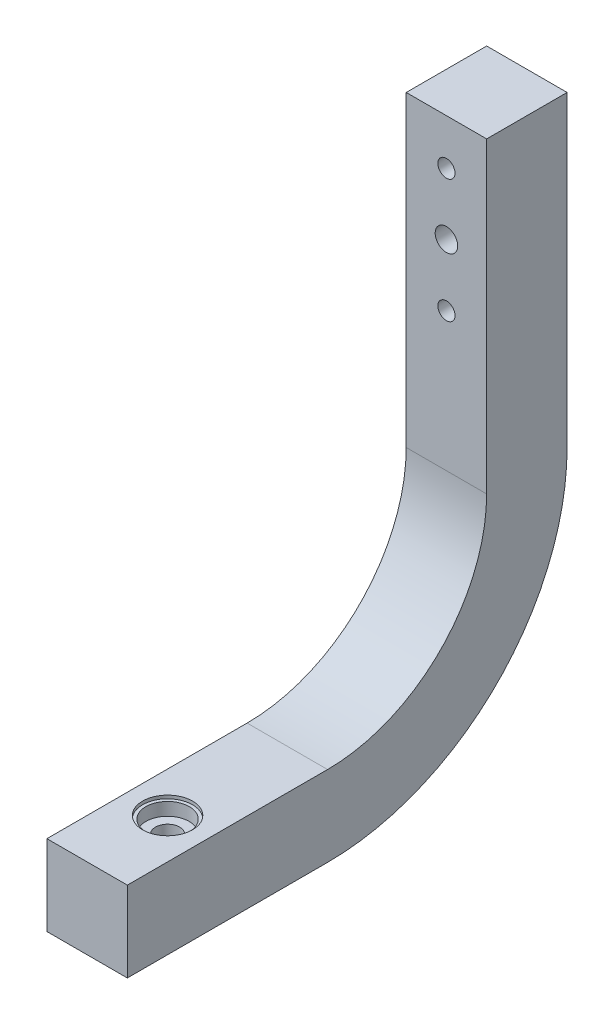
SolidWorks part; units mm, degrees
ref_plane "Front Plane" through (0, 0, 0) normal (0, 0, 1) x (1, 0, 0)
ref_plane "Top Plane" through (0, 0, 0) normal (0, 1, 0) x (1, 0, 0)
ref_plane "Right Plane" through (0, 0, 0) normal (1, 0, 0) x (0, 0, -1)
ref_axis "Z" through (0, 0, 86.1) along (0, 0, -1)
sketch "Sketch1" plane through (0, 0, 0) normal (1, 0, 0) x (0, 0, -1)
  line L0 (-15, 20) -> (0, 20)
  line L1 (0, 20) -> (0, -37.3333)
  line L2 (0, -32) -> (-50, -82) construction
  line L3 (-44.6667, -82) -> (-67, -82)
  line L4 (-67, -82) -> (-67, -67) construction
  line L5 (-67, -67) -> (-44.6667, -67)
  line L6 (-56.2132, -67) -> (-15, -25.7868) construction
  line L7 (-15, -37.3333) -> (-15, 20)
  line L8 (-35.6066, -46.3934) -> (-25, -57) construction
  line L9 (-44.6667, -67) -> (-56.2132, -67) construction
  line L10 (-67, -67) -> (-82, -67)
  line L11 (-67, -67) -> (-67, -82) construction
  line L12 (-67, -82) -> (-82, -82)
  line L13 (-82, -67) -> (-82, -82)
  line L14 (-15, -25.7868) -> (-15, -37.3333) construction
  line L15 (0, -37.3333) -> (0, -32) construction
  line L16 (-50, -82) -> (-44.6667, -82) construction
  arc A0 (-44.6667, -67) -> (-15, -37.3333) centre (-44.6667, -37.3333) ccw
  arc A1 (-44.6667, -82) -> (0, -37.3333) centre (-44.6667, -37.3333) ccw
  dimension "D1" = 15
  dimension "D2" = 67
  dimension "D3" = 82
  dimension "D4" = 20
  dimension "D5" = 135
  dimension "D6" = 50
  dimension "D7" = 15
  dimension "D8" = 22.3333
extrude "Boss-Extrude1" add sketch "Sketch1" along normal blind 7.5 and the other way blind 7.5
sketch "Sketch3" plane through (0, -67, 0) normal (0, 1, 0) x (1, 0, 0)
  line L0 (-8.25, 0) -> (8.25, 0) construction
  line L1 (0, -45.1) -> (0, 45.1) construction
  circle A0 centre (0, -67) radius 2.25
  dimension "D2" = 4.5
  dimension "D1" = 67
extrude "Cut-Extrude1" cut sketch "Sketch3" against normal through all
sketch "Sketch4" plane through (0, 0, 15) normal (0, 0, 1) x (1, 0, 0)
  line L0 (0, -11.5) -> (0, 11.5) construction
  circle A0 centre (0, 0) radius 2.1
  circle A1 centre (0, 11.5) radius 1.6
  circle A2 centre (0, -11.5) radius 1.6
  dimension "D1" = 4.2
  dimension "D3" = 3.2
  dimension "D2" = 23
extrude "Cut-Extrude2" cut sketch "Sketch4" against normal through all both and the other way through all
ref_axis "Axis1" through (0, -52.3642, 67) along (0, 1, 0)
sketch "Sketch5" plane through (0, 0, 0) normal (1, 0, 0) x (0, 0, -1)
  line L0 (-62.95, -79) -> (-62.95, -81.4)
  line L1 (-62.95, -81.4) -> (-62.35, -81.4)
  line L2 (-62.35, -81.4) -> (-62.35, -82)
  line L3 (-62.35, -82) -> (-67, -82)
  line L4 (-67, -82) -> (-67, -79)
  line L5 (-67, -79) -> (-62.95, -79)
  line L6 (-67, -74.5) -> (-67, -90.6731) construction
  line L7 (-67, -74.5) -> (-82, -74.5) construction
  line L8 (-67, -70) -> (-62.95, -70)
  line L9 (-67, -67) -> (-67, -70)
  line L10 (-62.35, -67) -> (-67, -67)
  line L11 (-62.35, -67.6) -> (-62.35, -67)
  line L12 (-62.95, -67.6) -> (-62.35, -67.6)
  line L13 (-62.95, -70) -> (-62.95, -67.6)
  line L16 (-67, -52.3642) -> (-67, -36.7401) construction
  line L17 (-82, -67) -> (-82, -82) construction
  line L18 (-67, -67) -> (-44.6667, -67) construction
  dimension "D2" = 4.65
  dimension "D3" = 3
  dimension "D4" = 8.1
revolve "Cut-Revolve1" cut sketch "Sketch5" angle 360 about axis through (0, -52.3642, 67) along (0, 1, 0)
equation "\"rbracket-width\"= \"L2Thickness\""
equation "\"D1@Boss-Extrude1\"=\"rbracket-width\"/2"
equation "\"D2@Boss-Extrude1\"=\"rbracket-width\"/2"
equation "\"EyeCaptureRadius\"= ( \"EyeDiameter\" + \"EyeClearance\" ) / 2"
equation "\"rbracket_planetocenterline_dist\"= \"BasePlaneDistance\""
equation "\"D2@Sketch1\"=\"rbracket_planetocenterline_dist\""
equation "\"EyeDiameter\" = 100"
equation "\"BasePlaneDistance\" = \"EyeDiameter\"/2+\"L2Thickness\"+\"EyeClearance\""
equation "\"EyeClearance\" = 2"
equation "\"D1@Sketch1\"=\"rbracket-width\""
equation "\"D3@Sketch1\"=(\"EyeDiameter\"+\"EyeClearance\"+\"EyeClearance\")/2 + \"L2Thickness\" + \"rbracket-width\""
equation "\"D6@Sketch1\"=\"EyeDiameter\"/2"
equation "\"D7@Sketch1\"=\"rbracket-width\""
equation "\"D1@Sketch3\"=\"BasePlaneDistance\""
equation "\"L2Thickness\" = 3.75 * \"shaft_diameter\""
equation "\"D8@Sketch1\"=\"rbracket_planetocenterline_dist\"/3"
equation "\"BearingFlangeOD\"= 7.5"
equation "\"BearingFlangeThickness\"= 0.75"
equation "\"BearingHousingID\"=4.5"
equation "\"BearingDepth\"= 6"
equation "\"PrinterFilamentThickness\"= 0.1"
equation "\"ApplyPrinterOffsets\"= 1"
equation "\"L2_ID\" = 20"
equation "\"vx\" = 0"
equation "\"vy\" = 0"
equation "\"vz\" = 100"
equation "\"parametric_end\" = 1"
equation "\"Rw_3_xx\" = -(\"vz\")/sqr((\"vx\")^2 + (\"vz\")^2)"
equation "\"Rw_3_xy\" = 0"
equation "\"Rw_3_xz\" = (\"vx\")/sqr((\"vx\")^2 + (\"vz\")^2)"
equation "\"Rw_3_zx\" = (\"vx\")/sqr((\"vx\")^2 + (\"vy\")^2 + (\"vz\")^2)"
equation "\"Rw_3_zy\" = (\"vy\")/sqr((\"vx\")^2 + (\"vy\")^2 + (\"vz\")^2)"
equation "\"Rw_3_zz\" = (\"vz\")/sqr((\"vx\")^2 + (\"vy\")^2 + (\"vz\")^2)"
equation "\"Rw_3_yx\" = (\"vx\")*(\"vy\")/sqr((\"vx\")^4 + (\"vx\")^2*(\"vy\")^2 + 2*(\"vx\")^2*(\"vz\")^2 + (\"vy\")^2*(\"vz\")^2 + (\"vz\")^4)"
equation "\"Rw_3_yy\" = -sqr((\"vx\")^2 + (\"vz\")^2)/sqr((\"vx\")^2 + (\"vy\")^2 + (\"vz\")^2)"
equation "\"Rw_3_yz\" = (\"vy\")*(\"vz\")/sqr((\"vx\")^4 + (\"vx\")^2*(\"vy\")^2 + 2*(\"vx\")^2*(\"vz\")^2 + (\"vy\")^2*(\"vz\")^2 + (\"vz\")^4)"
equation "\"O2Targx\" = -\"BasePlaneDistance\"*(\"vx\")*(\"vy\")/sqr((\"vx\")^4 + (\"vx\")^2*(\"vy\")^2 + 2*(\"vx\")^2*(\"vz\")^2 + (\"vy\")^2*(\"vz\")^2 + (\"vz\")^4)"
equation "\"O2Targy\" = \"BasePlaneDistance\"*sqr((\"vx\")^2 + (\"vz\")^2)/sqr((\"vx\")^2 + (\"vy\")^2 + (\"vz\")^2)"
equation "\"O2Targz\" = -\"BasePlaneDistance\"*(\"vy\")*(\"vz\")/sqr((\"vx\")^4 + (\"vx\")^2*(\"vy\")^2 + 2*(\"vx\")^2*(\"vz\")^2 + (\"vy\")^2*(\"vz\")^2 + (\"vz\")^4)"
equation "\"O2Targx_0\" = -(\"BasePlaneDistance\")*sqr((\"vx\")^2 + (\"vz\")^2)/sqr((\"vx\")^2 + (\"vy\")^2 + (\"vz\")^2)"
equation "\"O2Targy_0\" = -(\"BasePlaneDistance\")*(\"vy\")*(\"vz\")/sqr((\"vx\")^4 + (\"vx\")^2*(\"vy\")^2 + 2*(\"vx\")^2*(\"vz\")^2 + (\"vy\")^2*(\"vz\")^2 + (\"vz\")^4)"
equation "\"O2Targz_0\" = (\"BasePlaneDistance\")*(\"vx\")*(\"vy\")/sqr((\"vx\")^4 + (\"vx\")^2*(\"vy\")^2 + 2*(\"vx\")^2*(\"vz\")^2 + (\"vy\")^2*(\"vz\")^2 + (\"vz\")^4) + (\"BasePlaneDistance\")"
equation "\"theta2_s1\" = arcsin(((\"BasePlaneDistance\") - (\"O2Targz_0\"))/(\"BasePlaneDistance\")) + pi"
equation "\"theta2_s2\" = -arcsin(((\"BasePlaneDistance\") - (\"O2Targz_0\"))/(\"BasePlaneDistance\"))"
equation "\"theta1_s1\" = arcsin((\"O2Targy_0\")/((\"BasePlaneDistance\")*cos((\"Theta2\")))) + pi"
equation "\"theta1_s2\" = -arcsin((\"O2Targy_0\")/((\"BasePlaneDistance\")*cos((\"Theta2\"))))"
equation "\"theta1_s3\" = -arccos(-(\"O2Targx_0\")/((\"BasePlaneDistance\")*cos((\"Theta2\")))) + 2*pi"
equation "\"theta1_s4\" = arccos(-(\"O2Targx_0\")/((\"BasePlaneDistance\")*cos((\"Theta2\"))))"
equation "\"Theta1\" = \"theta1_s2\" 'so far, theta1_s1 and theta1_s4 have agreed, and they agree with the sw constraint solver"
equation "\"Theta2\" = \"theta2_s2\""
equation "\"o2_x\" = -(\"BasePlaneDistance\")*cos((\"Theta1\"))*cos((\"Theta2\"))"
equation "\"o2_y\" = -(\"BasePlaneDistance\")*sin((\"Theta1\"))*cos((\"Theta2\"))"
equation "\"o2_z\" = (\"BasePlaneDistance\")*(sin((\"Theta2\")) + 1)"
equation "\"o1_x\" = (\"BasePlaneDistance\")*sin((\"Theta1\"))"
equation "\"o1_y\" = -(\"BasePlaneDistance\")*cos((\"Theta1\"))"
equation "\"o1_z\" = (\"BasePlaneDistance\")"
equation "\"Actuator1_Theta\" = atn(\"vx\"/\"vz\") 'ik solution for the single link joint"
equation "\"Actuator2_Theta\" = \"Theta1\"  'ik solution for the double link joint"
equation "\"MotorBaseThickness\" = 3 "
equation "\"BaseThickness\" = 3 "
equation "\"EncoderToMagnetAirgap\" = 1 'Encoder to magnet airgap"
equation "\"EncoderHeight\" = 1.192  'Height of the encoder"
equation "\"MagnetThickness\" = 0.5  'Magnet thickness"
equation "\"pcb_thickness\" = 1.6  'Thickness of the PCB"
equation "\"pcb_outer_diameter\" = 32 'the OD of the pcb"
equation "\"shaft_diameter\" = 4"
equation "\"D2@Sketch3\"=\"shaft_diameter\"*1.125"
equation "\"D2@Sketch5\"=\"ApplyPrinterOffsets\"*\"PrinterFilamentThickness\"/2+4.6"
equation "\"D4@Sketch5\"=\"ApplyPrinterOffsets\"*\"PrinterFilamentThickness\"+8"
